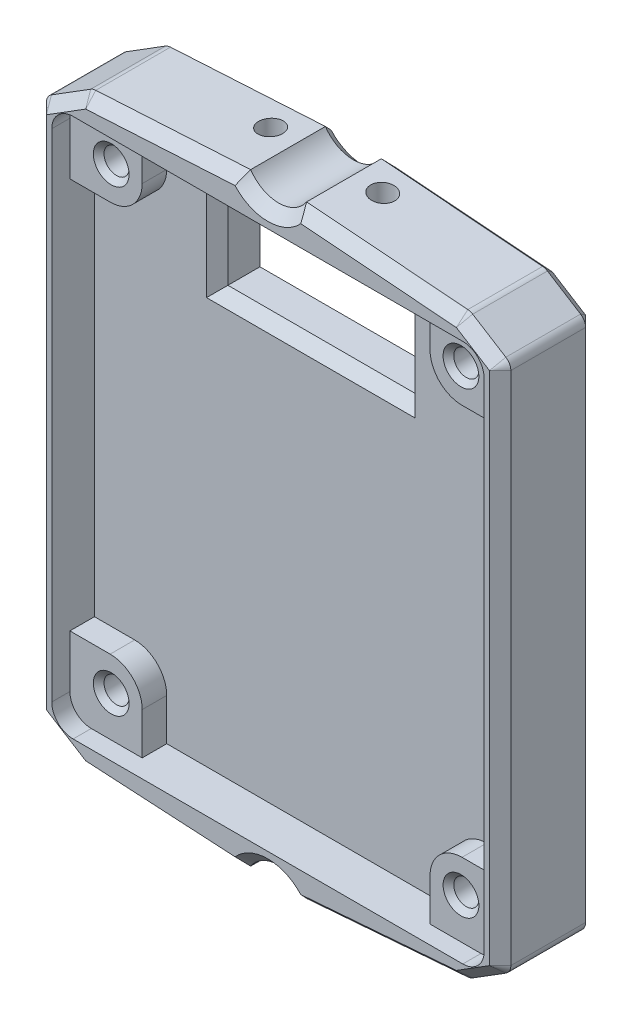
SolidWorks part; units mm, degrees
ref_plane "Front Plane" through (0, 0, 0) normal (0, 0, 1) x (1, 0, 0)
ref_plane "Top Plane" through (0, 0, 0) normal (0, 1, 0) x (1, 0, 0)
ref_plane "Right Plane" through (0, 0, 0) normal (1, 0, 0) x (0, 0, -1)
sketch "Sketch1" plane through (0, 0, 0) normal (0, 0, 1) x (1, 0, 0)
  line L0 (-23.25, 28.25) -> (-23.25, -28.25)
  line L1 (-20.25, 25.25) -> (20.25, 25.25)
  line L2 (-20.25, 25.25) -> (-20.25, -25.25)
  line L3 (-20.25, -25.25) -> (20.25, -25.25)
  line L4 (20.25, 25.25) -> (20.25, -25.25)
  line L5 (-20.25, 25.25) -> (20.25, -25.25) construction
  line L6 (-20.25, -25.25) -> (20.25, 25.25) construction
  line L7 (-23.25, -28.25) -> (23.25, -28.25)
  line L8 (23.25, 28.25) -> (23.25, -28.25)
  line L9 (-23.25, 28.25) -> (23.25, 28.25)
  point P0 (0, 0)
  dimension "D1" = 50.5
  dimension "D2" = 40.5
  dimension "D3" = 3
extrude "Boss-Extrude1" add sketch "Sketch1" along normal blind 4
sketch "Sketch2" plane through (0, 0, 0) normal (0, 0, -1) x (-1, 0, 0)
  line L1 (-23.25, 28.25) -> (23.25, 28.25)
  line L2 (-23.25, 28.25) -> (-23.25, -28.25)
  line L3 (-23.25, -28.25) -> (23.25, -28.25)
  line L4 (23.25, 28.25) -> (23.25, -28.25)
extrude "Boss-Extrude2" add sketch "Sketch2" along normal blind 5
sketch "Sketch3" plane through (0, 0, 0) normal (0, 0, 1) x (1, 0, 0)
  line L0 (0, 0) -> (0, 30.8352) construction
  line L1 (0, 0) -> (-31.9704, 0) construction
  line L2 (-20.25, 25.25) -> (-20.25, 18.3322)
  line L3 (-20.25, 25.25) -> (-20.25, -25.25) construction
  line L4 (-20.25, 18.3322) -> (-13.4806, 18.3322)
  line L5 (-13.4806, 18.3322) -> (-13.4806, 25.25)
  line L6 (20.25, 25.25) -> (-20.25, 25.25) construction
  line L7 (-13.4806, 25.25) -> (-20.25, 25.25)
  line L8 (13.4806, 25.25) -> (20.25, 25.25)
  line L9 (13.4806, 18.3322) -> (13.4806, 25.25)
  line L10 (20.25, 18.3322) -> (13.4806, 18.3322)
  line L11 (20.25, 25.25) -> (20.25, 18.3322)
  line L12 (20.25, -25.25) -> (20.25, -18.3322)
  line L13 (20.25, -18.3322) -> (13.4806, -18.3322)
  line L14 (13.4806, -18.3322) -> (13.4806, -25.25)
  line L15 (13.4806, -25.25) -> (20.25, -25.25)
  line L16 (-13.4806, -25.25) -> (-20.25, -25.25)
  line L17 (-13.4806, -18.3322) -> (-13.4806, -25.25)
  line L18 (-20.25, -18.3322) -> (-13.4806, -18.3322)
  line L19 (-20.25, -25.25) -> (-20.25, -18.3322)
  circle A0 centre (-16.38, 21.46) radius 1.175
  circle A1 centre (16.38, 21.46) radius 1.175
  circle A2 centre (16.38, -21.46) radius 1.175
  circle A3 centre (-16.38, -21.46) radius 1.175
  dimension "D3" = 2.35
  dimension "D1" = 21.46
  dimension "D2" = 16.38
extrude "Boss-Extrude3" add sketch "Sketch3" along normal blind 2.3
chamfer "Chamfer3" distance 4.5 angle 58 4 edges at (-23.25, -28.25, -0.5) (23.25, -28.25, -0.5) (-23.25, 28.25, -0.5) (23.25, 28.25, -0.5) first distance on face at (-23.25, 0, -0.5) first distance on face at (23.25, 0, -0.5)
fillet "Fillet1" radius 3 4 edges at (13.4806, -18.3322, 1.15) (-13.4806, -18.3322, 1.15) (13.4806, 18.3322, 1.15) (-13.4806, 18.3322, 1.15)
sketch "Sketch4" plane through (0, 0, 0) normal (0, 0, 1) x (1, 0, 0)
  line L0 (20.25, 25.25) -> (-20.25, 25.25) construction
  line L1 (-8.75, 23.8) -> (8.75, 23.8)
  line L2 (-8.75, 23.8) -> (-8.75, 13.8)
  line L3 (-8.75, 13.8) -> (8.75, 13.8)
  line L4 (8.75, 23.8) -> (8.75, 13.8)
  point P4 (0, 13.8)
  dimension "D1" = 10
  dimension "D2" = 1.45
  dimension "D3" = 17.5
extrude "Cut-Extrude1" cut sketch "Sketch4" against normal through all
sketch "Sketch5" plane through (0, 0, -5) normal (0, 0, -1) x (-1, 0, 0)
  line L0 (-29.5901, 0) -> (35.962, 0) construction
  line L4 (0, 42.4173) -> (0, 14.6256) construction
  line L8 (-23.25, -28.25) -> (23.25, -28.25)
  line L9 (23.25, -28.25) -> (23.25, -27.0847)
  line L10 (23.25, -27.0847) -> (2.6192, -28.25)
  line L11 (-23.25, -26.638) -> (-2.6192, -28.25)
  line L12 (-23.25, -28.25) -> (-23.25, -26.638)
  line L14 (16.0485, 28.25) -> (-16.0485, 28.25) construction
  line L15 (-2.6192, 28.25) -> (2.6192, 28.25)
  line L16 (-23.25, 28.25) -> (-23.25, 26.638)
  line L17 (-23.25, 26.638) -> (-2.6192, 28.25)
  line L18 (23.25, 27.0847) -> (2.6192, 28.25)
  line L19 (23.25, 28.25) -> (23.25, 27.0847)
  line L20 (-23.25, 28.25) -> (23.25, 28.25)
  arc A0 (-2.6192, 28.25) -> (2.6192, 28.25) centre (0, 30) ccw
  arc A1 (-2.6192, -28.25) -> (2.6192, -28.25) centre (0, -30) cw
  line M10 (-16.0485, -28.25) -> (16.0485, -28.25)
  line M12 (16.0485, 28.25) -> (-16.0485, 28.25)
  line M22 (16.0485, -28.25) -> (23.25, -23.75)
  line M23 (23.25, 23.75) -> (16.0485, 28.25)
  line M24 (-16.0485, 28.25) -> (-23.25, 23.75)
  line M25 (-23.25, -23.75) -> (-16.0485, -28.25)
  dimension "D1" = 6.3
  dimension "D3" = 60
extrude "Cut-Extrude2" cut sketch "Sketch5" against normal through all contours L12 L8 L11 M25 | A1 L8 | L9 L10 L8 M22 | L11 M25 M10 | L10 L8 M22 | L17 M24 M12 | L18 M23 M12 | L20 L18 L19 M23 | L20 L16 L17 M24 | A0 M12 | L11 A1 L10 L9 L8 L12 region at (20.2805, -27.5835, -5) region at (-12.0169, -27.972, -5) region at (0, -27.6777, -5) region at (12.2118, -27.8502, -5) region at (-20.1718, -27.7652, -5) region at (-12.0169, 27.972, -5) region at (12.2118, 27.8502, -5) region at (0, 27.6777, -5) region at (20.2805, 27.5835, -5) region at (-20.1718, 27.7652, -5)
sketch "Sketch6" plane through (0, 0, 4) normal (0, 0, 1) x (1, 0, 0)
  line L0 (-17.3831, -27.4161) -> (-2.6192, -28.25) construction
  line L1 (-23.2503, 33.2078) -> (-21.7503, 33.2078)
  line L2 (-23.2503, 33.2078) -> (-23.2503, -27.1694)
  line L3 (-23.2503, -27.1694) -> (-21.7503, -27.1694)
  line L4 (-21.7503, 33.2078) -> (-21.7503, -27.1694)
  line L5 (0, 0) -> (0, 31.5361) construction
  line L6 (21.7503, 33.2078) -> (21.7503, -27.1694)
  line L7 (23.2503, -27.1694) -> (21.7503, -27.1694)
  line L8 (23.2503, 33.2078) -> (23.2503, -27.1694)
  line L9 (23.2503, 33.2078) -> (21.7503, 33.2078)
  dimension "D1" = 1.5
extrude "Cut-Extrude3" cut sketch "Sketch6" against normal through all
sketch "Sketch7" plane through (0, 0, 0) normal (0, 1, 0) x (1, 0, 0)
  line L0 (-5.25, 1.5) -> (5.25, 1.5) construction
  line L1 (2.6192, 5) -> (-2.6192, 5) construction
  circle A0 centre (-5.25, 1.5) radius 1.125
  circle A1 centre (5.25, 1.5) radius 1.125
  point P4 (0, 1.5)
  dimension "D1" = 2.25
  dimension "D2" = 10.5
  dimension "D3" = 3.5
extrude "Cut-Extrude4" cut sketch "Sketch7" against normal blind 10 from offset 30
mirror "Mirror1" about plane through (0, 0, 0) normal (0, 1, 0) of "Cut-Extrude4"
fillet "Fillet2" radius 1 8 edges at (21.7503, -24.6871, -0.5) (17.9677, -27.0507, -0.5) (-17.3831, -27.4161, -0.5) (-21.7503, -24.6871, -0.5) (-21.7503, 24.6871, -0.5) (21.7503, 24.6871, -0.5) (-17.3831, 27.4161, -0.5) (17.9677, 27.0507, -0.5)
chamfer "Chamfer1" distance 1 angle 45 48 edges at (0, -26.85, 4) (0, 26.85, 4) (-9.8731, -27.8403, 4) (-21.7503, 0, 4) (10.1713, -27.6599, 4) (21.7503, 0, 4) (0, 23.8, 0) (-8.75, 18.8, 0) (8.75, 18.8, 0) (0, 13.8, 0) (0, 26.85, -5) (8.75, 18.8, -5) (0, 13.8, -5) (-8.75, 18.8, -5) (0, 23.8, -5) (-21.7503, 0, -5) (21.7503, 0, -5) (-9.8731, -27.8403, -5) (0, -26.85, -5) (10.1713, -27.6599, -5) (-17.3733, -27.3852, 4) (-19.4404, -26.1305, 4) (-19.4404, 26.1305, 4) (-21.6249, -24.6176, 4) (-21.6249, 24.6176, 4) (17.9585, -27.0226, 4) (19.7279, 25.9509, 4) (19.7279, -25.9509, 4) (21.6249, 24.6176, 4) (21.6249, -24.6176, 4) (-19.4404, 26.1305, -5) (19.7279, 25.9509, -5) (-21.6249, 24.6176, -5) (21.6249, 24.6176, -5) (-21.6249, -24.6176, -5) (21.6249, -24.6176, -5) (-19.4404, -26.1305, -5) (19.7279, -25.9509, -5) (-17.3733, -27.3852, -5) (17.9585, -27.0226, -5) (-9.8731, 27.8403, 4) (-17.3733, 27.3852, 4) (10.1713, 27.6599, 4) (17.9585, 27.0226, 4) (-9.8731, 27.8403, -5) (10.1713, 27.6599, -5) (-17.3733, 27.3852, -5) (17.9585, 27.0226, -5)
fillet "Fillet3" radius 2 4 edges at (-20.25, -25.25, 2.8088) (20.25, -25.25, 2.8088) (20.25, 25.25, 2.8088) (-20.25, 25.25, 2.8088)
sketch "Sketch8" plane through (0, 0, 2.3) normal (0, 0, 1) x (1, 0, 0)
  circle A0 centre (-16.38, 21.46) radius 1.175
  circle A1 centre (16.38, 21.46) radius 1.175
  circle A2 centre (16.38, -21.46) radius 1.175
  circle A3 centre (-16.38, -21.46) radius 1.175
  circle A4 centre (-16.38, 21.46) radius 1.175 construction
extrude "Cut-Extrude5" cut sketch "Sketch8" against normal through all
sketch "Sketch9" plane through (0, 0, -5) normal (0, 0, -1) x (-1, 0, 0)
  line L0 (0, 9.9819) -> (0, -23.9909) construction
  line L1 (-16.3742, -2.0365) -> (-6.3848, -2.0365)
  line L2 (-12.6187, -3.5365) -> (-6.3848, -3.5365)
  line L3 (-16.3742, -2.0365) -> (0, -17.5995)
  line L4 (-12.6187, -3.5365) -> (0, -15.5301)
  line L5 (-4, -2.7865) -> (-12.6323, -2.7865) construction
  line L6 (12.6187, -3.5365) -> (0, -15.5301)
  line L7 (16.3742, -2.0365) -> (0, -17.5995)
  line L8 (12.6187, -3.5365) -> (6.3848, -3.5365)
  line L9 (16.3742, -2.0365) -> (6.3848, -2.0365)
  arc A0 (-6.3848, -3.5365) -> (-6.3848, -2.0365) centre (-4, -2.7865) ccw
  arc A1 (6.3848, -3.5365) -> (6.3848, -2.0365) centre (4, -2.7865) cw
  dimension "D1" = 5
  dimension "D2" = 1.5
  dimension "D3" = 1.5
  dimension "D4" = 8
extrude "Cut-Extrude6" cut sketch "Sketch9" against normal blind 1
chamfer "Chamfer2" distance 0.5 angle 45 4 edges at (-17.555, -21.46, 2.3) (17.555, -21.46, 2.3) (15.205, 21.46, 2.3) (-15.205, 21.46, 2.3)
chamfer "Chamfer4" distance 1 angle 45 10 edges at (-8.1871, -9.818, -5) (-11.3795, -2.0365, -5) (-1.5, -2.7865, -5) (-9.5018, -3.5365, -5) (-6.3093, -9.5333, -5) (6.3093, -9.5333, -5) (9.5018, -3.5365, -5) (1.5, -2.7865, -5) (11.3795, -2.0365, -5) (8.1871, -9.818, -5)
